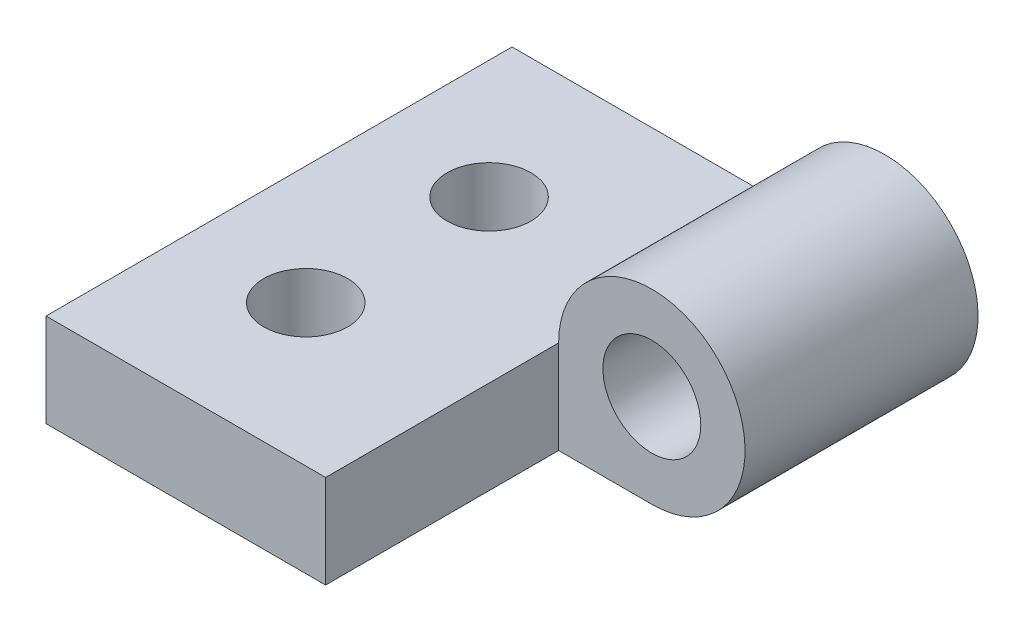
SolidWorks part; units mm, degrees
ref_plane "Front Plane" through (0, 0, 0) normal (0, 0, 1) x (1, 0, 0)
ref_plane "Top Plane" through (0, 0, 0) normal (0, 1, 0) x (1, 0, 0)
ref_plane "Right Plane" through (0, 0, 0) normal (1, 0, 0) x (0, 0, -1)
sketch "Sketch1" plane through (0, 0, 0) normal (0, 0, 1) x (1, 0, 0)
  line L0 (0, 5.08) -> (15.24, 5.08)
  line L1 (0, 0) -> (20.32, 0)
  line L2 (0, 0) -> (0, 5.08)
  circle A2 centre (20.32, 5.08) radius 2.667
  arc A3 (20.32, 0) -> (15.24, 5.08) centre (20.32, 5.08) ccw
  point P7 (0, 0)
  dimension "D1" = 10.16
  dimension "D2" = 5.334
  dimension "D3" = 5.08
  dimension "D4" = 15.24
extrude "Boss-Extrude1" add sketch "Sketch1" along normal blind 25.4
sketch "Sketch2" plane through (0, 0, 25.4) normal (0, 0, 1) x (1, 0, 0)
  line L0 (15.24, 10.16) -> (15.24, 0)
  line L2 (0, 0) -> (20.32, 0) construction
  line L3 (15.24, 0) -> (20.32, 0)
  line L4 (15.24, 10.16) -> (20.32, 10.16)
  line L5 (0, 0) -> (20.32, 0) construction
  arc A0 (20.32, 0) -> (20.32, 10.16) centre (20.32, 5.08) ccw
  point P2 (17.2036, 10.1926)
  point P3 (17.78, 0)
  point P11 (17.2036, 0)
  dimension "D1" = 5.08
  dimension "D3" = 10.16
extrude "Cut-Extrude1" cut sketch "Sketch2" against normal blind 12.7
sketch "Sketch3" plane through (0, 5.08, 0) normal (0, 1, 0) x (1, 0, 0)
  line L0 (6.4516, -5.4187) -> (6.4516, 0) construction
  line L1 (15.24, 0) -> (0, 0) construction
  line L2 (6.4516, -9.9907) -> (6.4516, -15.4093) construction
  line L4 (6.4516, -19.9813) -> (6.4516, -25.4) construction
  line L5 (15.24, -25.4) -> (0, -25.4) construction
  line L6 (15.24, -25.4) -> (15.24, -12.7) construction
  circle A0 centre (6.4516, -7.7047) radius 2.286
  circle A1 centre (6.4516, -17.6953) radius 2.286
  dimension "D1" = 4.572
  dimension "D2" = 8.7884
extrude "Cut-Extrude2" cut sketch "Sketch3" against normal through all
